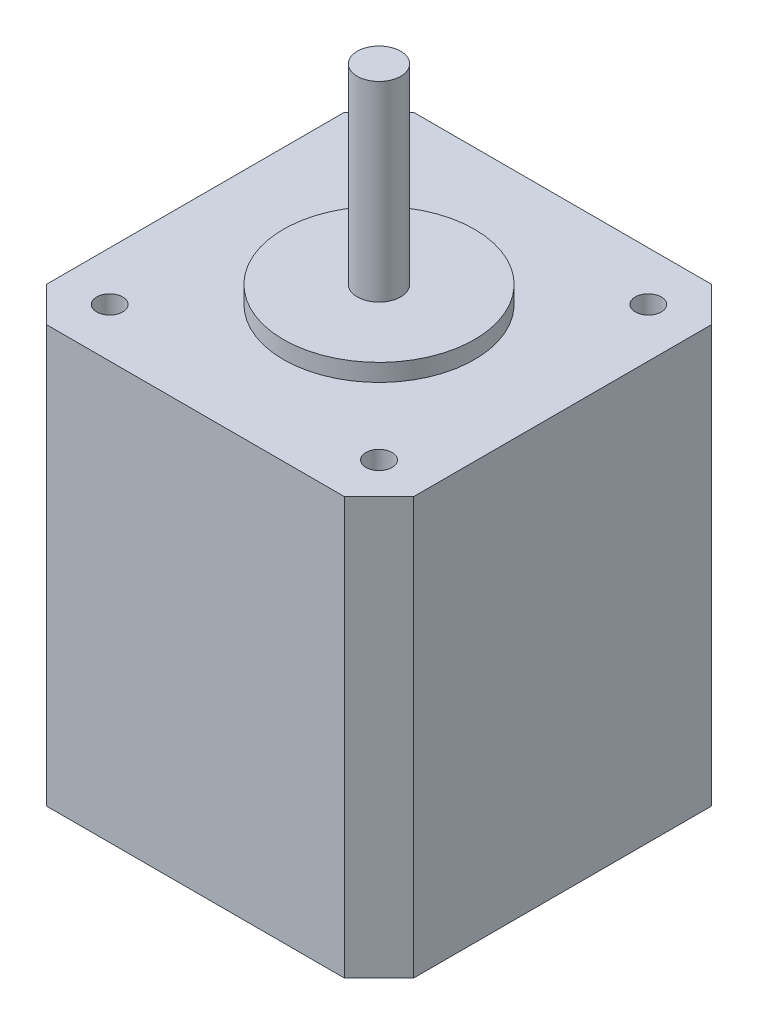
SolidWorks part; units mm, degrees
ref_plane "Front Plane" through (0, 0, 0) normal (0, 0, 1) x (1, 0, 0)
ref_plane "Top Plane" through (0, 0, 0) normal (0, 1, 0) x (1, 0, 0)
ref_plane "Right Plane" through (0, 0, 0) normal (1, 0, 0) x (0, 0, -1)
sketch "Sketch1" plane through (0, 0, 0) normal (0, 1, 0) x (1, 0, 0)
  line L1 (-21.15, -21.15) -> (21.15, -21.15)
  line L2 (-21.15, -21.15) -> (-21.15, 21.15)
  line L3 (-21.15, 21.15) -> (21.15, 21.15)
  line L4 (21.15, -21.15) -> (21.15, 21.15)
  line L5 (-21.15, -21.15) -> (21.15, 21.15) construction
  line L6 (-21.15, 21.15) -> (21.15, -21.15) construction
  point P0 (0, 0)
  dimension "D1" = 42.3
  dimension "D2" = 42.3
extrude "Boss-Extrude1" add sketch "Sketch1" along normal blind 48
sketch "Sketch2" plane through (0, 48, 0) normal (0, 1, 0) x (1, 0, 0)
  line L0 (0, 0) -> (0, 21.15) construction
  line L1 (21.15, 21.15) -> (-21.15, 21.15) construction
  line L2 (21.15, 0) -> (-21.15, 0) construction
  line L3 (21.15, -21.15) -> (21.15, 21.15) construction
  line L4 (-21.15, 21.15) -> (-21.15, -21.15) construction
  line L5 (0, 0) -> (0, -21.15) construction
  line L6 (-21.15, -21.15) -> (21.15, -21.15) construction
  line L7 (-21.15, 17.15) -> (-17.15, 21.15)
  line L8 (21.15, 17.15) -> (17.15, 21.15)
  line L9 (-21.15, -17.15) -> (-17.15, -21.15)
  line L10 (21.15, -17.15) -> (17.15, -21.15)
  circle A0 centre (-15.5, 15.5) radius 1.5
  circle A2 centre (15.5, 15.5) radius 1.5
  circle A3 centre (15.5, -15.5) radius 1.5
  circle A4 centre (-15.5, -15.5) radius 1.5
  circle A5 centre (0, 0) radius 11
  circle A6 centre (0, 0) radius 2.5
  point P32 (0, 0)
  line M1 (21.15, -21.15) -> (21.15, 21.15)
  line M2 (21.15, 21.15) -> (-21.15, 21.15)
  line M3 (-21.15, 21.15) -> (-21.15, -21.15)
  line M4 (-21.15, -21.15) -> (21.15, -21.15)
  dimension "D1" = 3
  dimension "D2" = 5.65
  dimension "D3" = 5.65
  dimension "D4" = 22
  dimension "D5" = 5
  dimension "D6" = 4
  dimension "D7" = 4
extrude "Cut-Extrude1" cut sketch "Sketch2" against normal through all contours L7 M3 M2 | L8 M1 M2 | L10 M1 M4 | L9 M3 M4 region at (-19.8167, 48, -19.8167) region at (-19.8167, 48, 19.8167) region at (19.8167, 48, -19.8167) region at (19.8167, 48, 19.8167)
extrude "Cut-Extrude2" cut sketch "Sketch2<3>" against normal blind 4.5 contours A2 | A3 | A4 | A0 region at (15.5, 48, -15.5) region at (15.5, 48, 15.5) region at (-15.5, 48, 15.5)
sketch "Sketch2<3>" plane through (0, 48, 0) normal (0, 1, 0) x (1, 0, 0) same geometry as "Sketch2"
extrude "Boss-Extrude2" add sketch "Sketch2<4>" along normal blind 2 contours A5
sketch "Sketch2<4>" plane through (0, 48, 0) normal (0, 1, 0) x (1, 0, 0) same geometry as "Sketch2"
extrude "Boss-Extrude3" add sketch "Sketch2<5>" along normal blind 24 contours A6
sketch "Sketch2<5>" plane through (0, 48, 0) normal (0, 1, 0) x (1, 0, 0) same geometry as "Sketch2"
